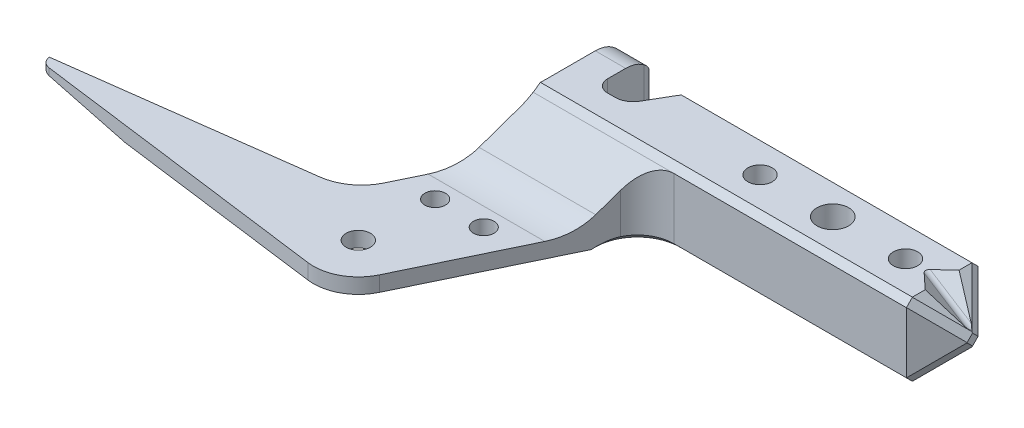
SolidWorks part; units mm, degrees
note: The reader was unsure of these and kept them because the rebuilt part matched: shared geometry of "Sketch1<6>".
material "AISI 440C (55-60 HRC)"
ref_plane "Front Plane" through (0, 0, 0) normal (0, 0, 1) x (1, 0, 0)
ref_plane "Top Plane" through (0, 0, 0) normal (0, 1, 0) x (1, 0, 0)
ref_plane "Right Plane" through (0, 0, 0) normal (1, 0, 0) x (0, 0, -1)
sketch "Sketch1" plane through (0, 0, 0) normal (0, 1, 0) x (1, 0, 0)
  line L1 (-50, 0.875) -> (-7.9044, 6.417)
  line L2 (-50, -0.875) -> (-0.9651, -7.3306)
  line L3 (-50, 0.875) -> (-50, -0.875) construction
  line L4 (-50, -0.875) -> (-50, 0) construction
  line L5 (-50, 0) -> (0, 0) construction
  line L6 (-51.5464, 0.6714) -> (-50, 0.875)
  line L12 (45.2, 0) -> (45.2, 35) construction
  line L13 (45.2, 0) -> (57.1707, 32.8892) construction
  line L14 (20.2, -13.0705) -> (20.2, 13.6744) construction
  line L15 (6.6619, -3.2074) -> (21.2, 26.9892)
  line L24 (20.2, 26.9892) -> (68.2, 26.9892)
  line L25 (20.2, 26.9892) -> (20.2, 38.7892)
  line L28 (20.2, 38.7892) -> (68.2, 38.7892)
  line L32 (68.2, 26.9892) -> (68.2, 38.7892)
  line L37 (20.2, 26.9892) -> (2, 26.9892)
  line L38 (25.2, 26.9392) -> (68.2, 26.9392) construction
  line L39 (20.2, 21.9892) -> (25.2, 26.9392) construction
  line L40 (12, 32) -> (7, 32)
  line L41 (7, 32) -> (7, 42)
  line L42 (7, 42) -> (2, 42)
  line L43 (2, 42) -> (2, 26.9892)
  line L44 (2, 26.9892) -> (-7.9044, 6.417)
  line L46 (12, 32) -> (15.9198, 38.7892)
  line L47 (15.9198, 38.7892) -> (20.2, 38.7892)
  circle A0 centre (0, 0) radius 2 construction
  arc A1 (-50, -0.875) -> (-51.5464, 0.6714) centre (-49.7655, 0.9059) cw
  circle A5 centre (0, 0) radius 38.4 construction
  arc A8 (-0.9651, -7.3306) -> (6.6619, -3.2074) centre (0, 0) ccw
  circle A11 centre (45.2, 0) radius 6.8 construction
  circle A12 centre (45.2, 0) radius 35 construction
  circle A13 centre (57.1707, 32.8892) radius 2 construction
  circle A14 centre (45.2, 32.8892) radius 2.5 construction
  circle A15 centre (33.2293, 32.8892) radius 2 construction
  point P32 (20.2, 32.8892)
  dimension "D1" = 4
  dimension "D6" = 13.6
  dimension "D7" = 76.8
  dimension "D16" = 0.1
  dimension "D17" = 5
  dimension "D18" = 5
  dimension "D20" = 5
  dimension "D19" = 42
  dimension "D22" = 60
  dimension "D8" = 70
  dimension "D10" = 5
  dimension "D12" = 25
  dimension "D13" = 11.8
  dimension "D14" = 48
  dimension "D15" = 1
  dimension "D9" = 4
  dimension "D2" = 7.5
  dimension "D3" = 7.5
  dimension "D4" = 1.75
  dimension "D5" = 50
  dimension "D11" = 20
  dimension "D23" = 32
  dimension "D24" = 5
  dimension "D25" = 2
extrude "Boss-Extrude1" add sketch "Sketch1" along normal blind 2.5
extrude "Boss-Extrude2" add sketch "Sketch1<6>" along normal blind 12
sketch "Sketch1<6>" plane through (0, 0, 0) normal (0, 1, 0) x (1, 0, 0) same geometry as "Sketch1"
hole_wizard "Ø4.0 (4) Diameter Hole1" positions "Sketch2" profile "Sketch3" hole size "Ø4.0" standard "ANSI Metric" end condition through all
sketch "Sketch2" plane through (0, 0, 0) normal (0, -1, 0) x (-1, 0, 0)
  point P0 (-57.1707, 32.8892)
  point P3 (-33.2293, 32.8892)
sketch "Sketch3" plane through (57.1707, 0, -32.8892) normal (1, 0, 0) x (0, 0, -1)
  line L0 (0, 0) -> (0, 12)
  line L1 (0, 12) -> (2, 12)
  line L2 (2, 12) -> (2, 0)
  line L5 (2, 0) -> (0, 0)
  line L11 (0, -6.35) -> (0, 107.95) construction
  dimension "Thru Hole Dia." = 4
  dimension "Thru Hole Depth" = 12
hole_wizard "Ø4.0 (4) Diameter Hole2" positions "Sketch9" profile "Sketch10" hole size "Ø4.0" standard "ANSI Metric" end condition through all
sketch "Sketch9" plane through (0, 0, 0) normal (0, -1, 0) x (-1, 0, 0)
  point P0 (0, 0)
sketch "Sketch10" plane through (0, 0, 0) normal (1, 0, 0) x (0, 0, -1)
  line L0 (0, 0) -> (0, 12)
  line L1 (0, 12) -> (2, 12)
  line L2 (2, 12) -> (2, 0)
  line L5 (2, 0) -> (0, 0)
  line L11 (0, -6.35) -> (0, 107.95) construction
  dimension "Thru Hole Dia." = 4
  dimension "Thru Hole Depth" = 12
hole_wizard "Ø5.2 (5.2) Diameter Hole1" positions "Sketch4" profile "Sketch5" hole size "Ø5.2" standard "ANSI Metric" end condition through all
sketch "Sketch4" plane through (0, 0, 0) normal (0, -1, 0) x (-1, 0, 0)
  point P0 (-45.2, 32.8892)
sketch "Sketch5" plane through (45.2, 0, -32.8892) normal (1, 0, 0) x (0, 0, -1)
  line L0 (0, 0) -> (0, 12)
  line L1 (0, 12) -> (2.6, 12)
  line L2 (2.6, 12) -> (2.6, 0)
  line L5 (2.6, 0) -> (0, 0)
  line L11 (0, -6.35) -> (0, 107.95) construction
  dimension "Thru Hole Dia." = 5.2
  dimension "Thru Hole Depth" = 12
chamfer "Chamfer5" distance 8.5 angle 45 1 edges at (11.6, 2.5, -26.9892)
fillet "Fillet13" radius 6 1 edges at (21.2, 5.5, -26.9892)
chamfer "Chamfer1" distance 5 angle 45 4 edges at (68.2, 0, -32.8892) (68.2, 12, -32.8892) (68.2, 6, -38.7892) (68.2, 6, -26.9892)
chamfer "Chamfer2" distance 1 angle 45 5 edges at (44.0852, 0, -26.9892) (32.6, 12, -26.9892) (39.5599, 12, -38.7892) (39.5599, 0, -38.7892) (21.778, 0, -26.0694)
chamfer "Chamfer4" distance 0.8 4 edges at (65.95, 2.75, -36.0392) (65.95, 9.25, -36.0392) (65.95, 9.25, -29.7392) (65.95, 2.75, -29.7392)
ref_plane "Plane1" through (0, 0, -32.8892) normal (0, 0, 1) x (1, 0, 0)
sketch "Sketch7" plane through (0, 0, -32.8892) normal (0, 0, 1) x (1, 0, 0)
  line L1 (68.2, 6.9202) -> (60.2, 12)
  line L2 (2, 12) -> (63.2, 12) construction
  line L3 (60.2, 12) -> (60.2, 14)
  line L7 (60.2, 14) -> (68.2, 14)
  line L8 (68.2, 14) -> (68.2, 6.9202)
  dimension "D1" = 2
  dimension "D2" = 8
revolve "Cut-Revolve1" cut sketch "Sketch7" angle 60 about L1
fillet "Fillet4" radius 1 1 edges at (64.2, 9.4601, -32.8892)
fillet "Fillet5" radius 8 3 edges at (7.5077, 2.5, -18.4892) (-7.9044, 1.25, -6.417) (2, 5.5, -26.9892)
fillet "Fillet6" radius 3 2 edges at (15.9198, 6, -38.7892) (12, 6, -32)
fillet "Fillet7" radius 2 1 edges at (7, 6, -32)
fillet "Fillet11" radius 5 2 edges at (4.5, 0, -42) (4.5, 12, -42)
fillet "Fillet12" radius 2 2 edges at (7, 6, -42) (2, 6, -42)
fillet "Chamfer6" [suppressed] radius 2.5
chamfer "Chamfer7" [suppressed] distance 2.5 angle 45
sketch "Sketch8" plane through (2, 0, -0.502) normal (-1, 0, 0) x (0, 0, 1)
  line L0 (-41.498, 7) -> (-41.498, 5) construction
  line L1 (2.502, 2.5) -> (-1.498, 2.5) construction
  circle A0 centre (-13.498, 2.5) radius 28 construction
  dimension "D1" = 56
ref_plane "Plane2" through (-50.5813, 0, 6.6592) normal (0.9914, 0, -0.1305) x (0, -1, 0)
sketch "Sketch11" plane through (-50.5813, 0, 6.6592) normal (0.9914, 0, -0.1305) x (0, -1, 0)
  line L0 (-2, 7.3938) -> (0, 1.8989)
  line L1 (-2.5, 7.3938) -> (0, 7.3938) construction
  line L2 (0, 1.8989) -> (0, 7.3938)
  line L3 (0, 7.3938) -> (-2, 7.3938)
  dimension "D1" = 2
  dimension "D2" = 70
extrude "Cut-Extrude2" cut sketch "Sketch11" along normal blind 38
chamfer "Chamfer8" distance 2.5 angle 70 1 edges at (-13.5129, 0, -2.9074)
fillet "Fillet14" radius 3 1 edges at (-9.4269, 1, -3.4454)
sketch "Esquisse1" plane through (0, 2.5, 0) normal (0, 1, 0) x (1, 0, 0)
  line L0 (-5.132, 12.1755) -> (14.068, 12.1755) construction
  line L1 (-3.6877, 15.1755) -> (-6.0284, 10.3137) construction
  line L2 (6.6619, -3.2074) -> (15.5123, 15.1755) construction
  line L4 (15.5123, 15.1755) -> (-3.6877, 15.1755) construction
  circle A0 centre (0.468, 12.1755) radius 1.7 construction
  circle A1 centre (8.468, 12.1755) radius 1.7 construction
  point P12 (4.468, 12.1755)
  dimension "D2" = 3.4
  dimension "D1" = 4
  dimension "D3" = 4
  dimension "D4" = 3
hole_wizard "M3 Clearance Hole1" positions "Esquisse2" profile "Esquisse3" hole size "M3" standard "ANSI Metric" end condition up to next
sketch "Esquisse2" plane through (0, 2.5, 0) normal (0, 1, 0) x (1, 0, 0)
  point P0 (0.468, 12.1755)
  point P3 (8.468, 12.1755)
sketch "Esquisse3" plane through (0.468, 2.5, -12.1755) normal (1, 0, 0) x (0, 0, 1)
  line L0 (0, 0) -> (0, 2.5)
  line L1 (0, 2.5) -> (1.7, 2.5)
  line L2 (1.7, 2.5) -> (1.7, 0)
  line L5 (1.7, 0) -> (0, 0)
  line L11 (0, -6.35) -> (0, 107.95) construction
  dimension "Thru Hole Dia." = 3.4
  dimension "Thru Hole Depth" = 2.5
